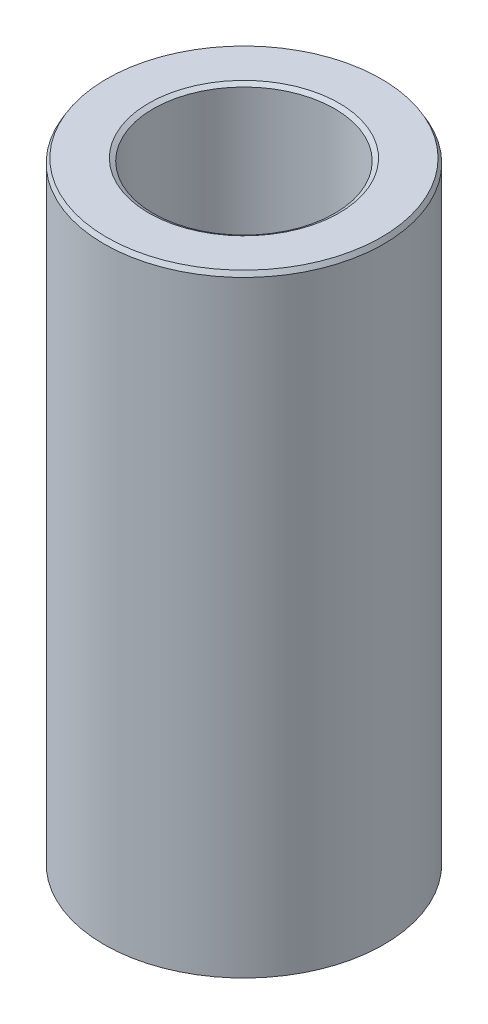
SolidWorks part; units mm, degrees
ref_plane "Front Plane" through (0, 0, 0) normal (0, 0, 1) x (1, 0, 0)
ref_plane "Top Plane" through (0, 0, 0) normal (0, 1, 0) x (1, 0, 0)
ref_plane "Right Plane" through (0, 0, 0) normal (1, 0, 0) x (0, 0, -1)
sketch "Sketch1" plane through (0, 0, 0) normal (0, 1, 0) x (1, 0, 0)
  circle A0 centre (0, 0) radius 57.5
  dimension "SLEEVE_OD" = 115
extrude "Boss-Extrude1" add sketch "Sketch1" along normal blind 252.3465
sketch "Sketch2" plane through (0, 0, 0) normal (0, 1, 0) x (1, 0, 0)
  circle A0 centre (0, 0) radius 37.2956
  dimension "BORE_D" = 74.5912
extrude "Cut-Extrude1" cut sketch "Sketch2" along normal through all
chamfer "Chamfer1" distance 1.8434 angle 30 4 edges at (0, 252.3465, 37.2956) (0, 0, 37.2956) (0, 0, 57.5) (0, 252.3465, 57.5) first distance on face at (0, 252.3465, 37.2956) first distance on face at (0, 0, 37.2956) first distance on face at (0, 252.3465, 57.5)
